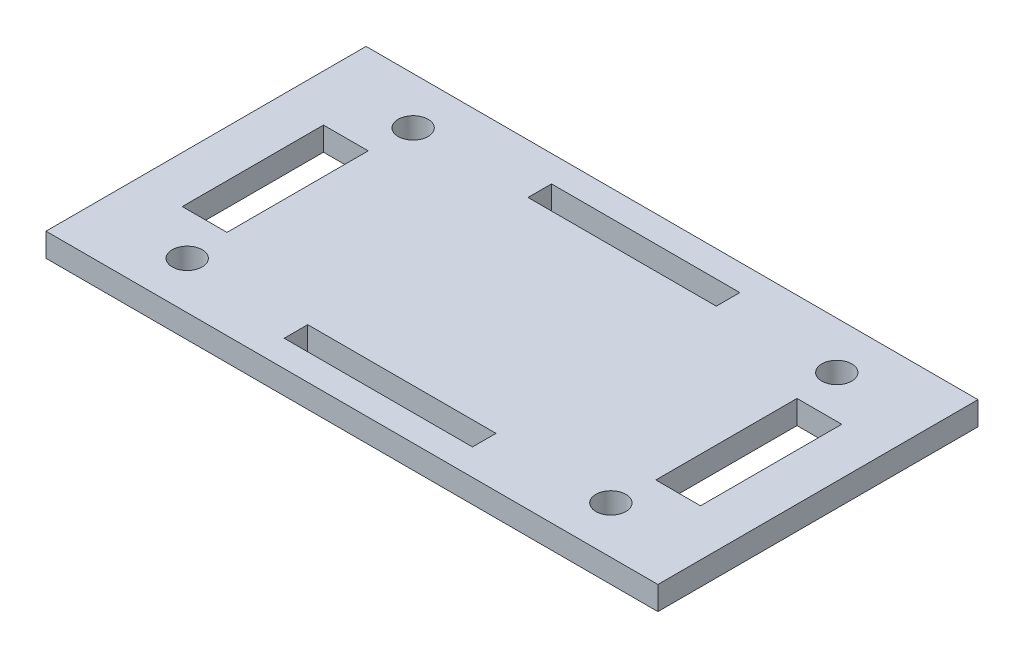
SolidWorks part; units mm, degrees
ref_plane "Front" through (0, 0, 0) normal (0, 0, 1) x (1, 0, 0)
ref_plane "Top" through (0, 0, 0) normal (0, 1, 0) x (1, 0, 0)
ref_plane "Right" through (0, 0, 0) normal (1, 0, 0) x (0, 0, -1)
sketch "Sketch1" plane through (0, 0, 0) normal (0, 1, 0) x (1, 0, 0)
  line L0 (0, 10.0965) -> (40.64, 10.0965) construction
  line L1 (0, 0) -> (40.64, 0)
  line L2 (0, 0) -> (0, 20.193)
  line L3 (0, 20.193) -> (40.64, 20.193)
  line L4 (40.64, 0) -> (40.64, 20.193)
  line L5 (-20.955, -11.4935) -> (61.595, -11.4935)
  line L6 (-20.955, -11.4935) -> (-20.955, 31.6865)
  line L7 (-20.955, 31.6865) -> (61.595, 31.6865)
  line L8 (61.595, -11.4935) -> (61.595, 31.6865)
  line L9 (44.323, 16.0655) -> (44.323, 4.1275) construction
  line L10 (20.32, 20.193) -> (20.32, 0) construction
  line L11 (7.62, -7.9375) -> (33.02, -7.9375)
  line L12 (7.62, 24.9555) -> (33.02, 24.9555)
  line L13 (7.62, 24.9555) -> (7.62, 28.1305)
  line L14 (7.62, 28.1305) -> (33.02, 28.1305)
  line L15 (33.02, 24.9555) -> (33.02, 28.1305)
  line L16 (-14.6368, 19.6215) -> (-8.6043, 19.6215)
  line L17 (-14.6368, 19.6215) -> (-14.6367, 0.5715)
  line L18 (-14.6367, 0.5715) -> (-8.6042, 0.5715)
  line L19 (-8.6043, 19.6215) -> (-8.6042, 0.5715)
  line L20 (33.02, -4.7625) -> (33.02, -7.9375)
  line L21 (7.62, -4.7625) -> (33.02, -4.7625)
  line L22 (7.62, -4.7625) -> (7.62, -7.9375)
  line L23 (55.2767, 0.5715) -> (49.2443, 0.5715)
  line L24 (49.2443, 19.6215) -> (49.2443, 0.5715)
  line L25 (55.2767, 19.6215) -> (49.2443, 19.6215)
  line L26 (55.2767, 19.6215) -> (55.2767, 0.5715)
  circle A0 centre (44.323, 16.0655) radius 2.159
  circle A1 centre (44.323, 4.1275) radius 2.159
  circle A2 centre (-3.683, 4.1275) radius 2.159
  circle A3 centre (-3.683, 16.0655) radius 2.159
  point P12 (20.32, 31.6865)
  point P14 (-20.955, 10.0965)
  point P19 (44.323, 10.0965)
  point P20 (20.32, 28.1305)
  point P22 (7.62, 26.543)
  point P35 (-8.6042, 10.0965)
  point P36 (-11.6205, 0.5715)
  dimension "D5" = 4.318
  dimension "D1" = 20.193
  dimension "D2" = 40.64
  dimension "D3" = 82.55
  dimension "D4" = 43.18
  dimension "D6" = 4.1275
  dimension "D7" = 3.683
  dimension "D8" = 3.175
  dimension "D9" = 25.4
  dimension "D10" = 6.35
  dimension "D11" = 6.0325
  dimension "D12" = 19.05
  dimension "D13" = 7.9375
extrude "Boss-Extrude1" add sketch "Sketch1" along normal blind 3.175
sketch "Sketch2" plane through (0, 3.175, 0) normal (0, 1, 0) x (1, 0, 0)
  line L0 (40.64, 0) -> (40.64, 20.193) construction
  line L1 (40.64, 13.2715) -> (43.815, 13.2715)
  line L2 (40.64, 13.2715) -> (40.64, 6.9215)
  line L3 (40.64, 6.9215) -> (43.815, 6.9215)
  line L4 (43.815, 13.2715) -> (43.815, 6.9215)
  point P6 (40.64, 10.0965)
  point P7 (43.815, 10.0965)
  dimension "D1" = 6.35
  dimension "D2" = 3.175
extrude "Cut-Extrude1" cut sketch "Sketch2" against normal up to surface (3.175 mm away)
sketch "Sketch3" plane through (0, 3.175, 0) normal (0, 1, 0) x (1, 0, 0)
  line L0 (-8.6042, 0.5715) -> (-8.6042, 19.6215) construction
  line L1 (-8.6042, 20.193) -> (49.2443, 20.193)
  line L2 (-8.6042, 20.193) -> (-8.6042, 0)
  line L3 (-8.6042, 0) -> (49.2443, 0)
  line L4 (49.2443, 20.193) -> (49.2443, 0)
  line L5 (49.2443, 19.6215) -> (49.2443, 0.5715) construction
  line L6 (0, 0) -> (40.64, 0) construction
  line L7 (40.64, 20.193) -> (0, 20.193) construction
extrude "Boss-Extrude2" add sketch "Sketch3" against normal up to surface (3.175 mm away)
sketch "Sketch4" plane through (0, 3.175, 0) normal (0, 1, 0) x (1, 0, 0)
  line L0 (61.595, -11.4935) -> (61.595, 31.6865) construction
  line L1 (-20.955, -11.4935) -> (61.595, -11.4935) construction
  line L2 (61.595, 10.0965) -> (-20.955, 10.0965) construction
  line L3 (-20.955, 31.6865) -> (-20.955, -11.4935) construction
  line L5 (61.595, 31.6865) -> (-20.955, 31.6865) construction
  line L6 (20.32, 31.6865) -> (20.32, -11.4935) construction
  circle A0 centre (48.895, -5.1435) radius 2.0193
  circle A1 centre (-8.255, -5.1435) radius 2.0193
  circle A2 centre (-8.255, 25.3365) radius 2.0193
  circle A3 centre (48.895, 25.3365) radius 2.0193
  dimension "D3" = 4.0386
  dimension "D1" = 12.7
  dimension "D2" = 6.35
extrude "Cut-Extrude2" cut sketch "Sketch4" against normal up to surface (3.175 mm away) up to face at (52.2605, 0, -10.0965)
